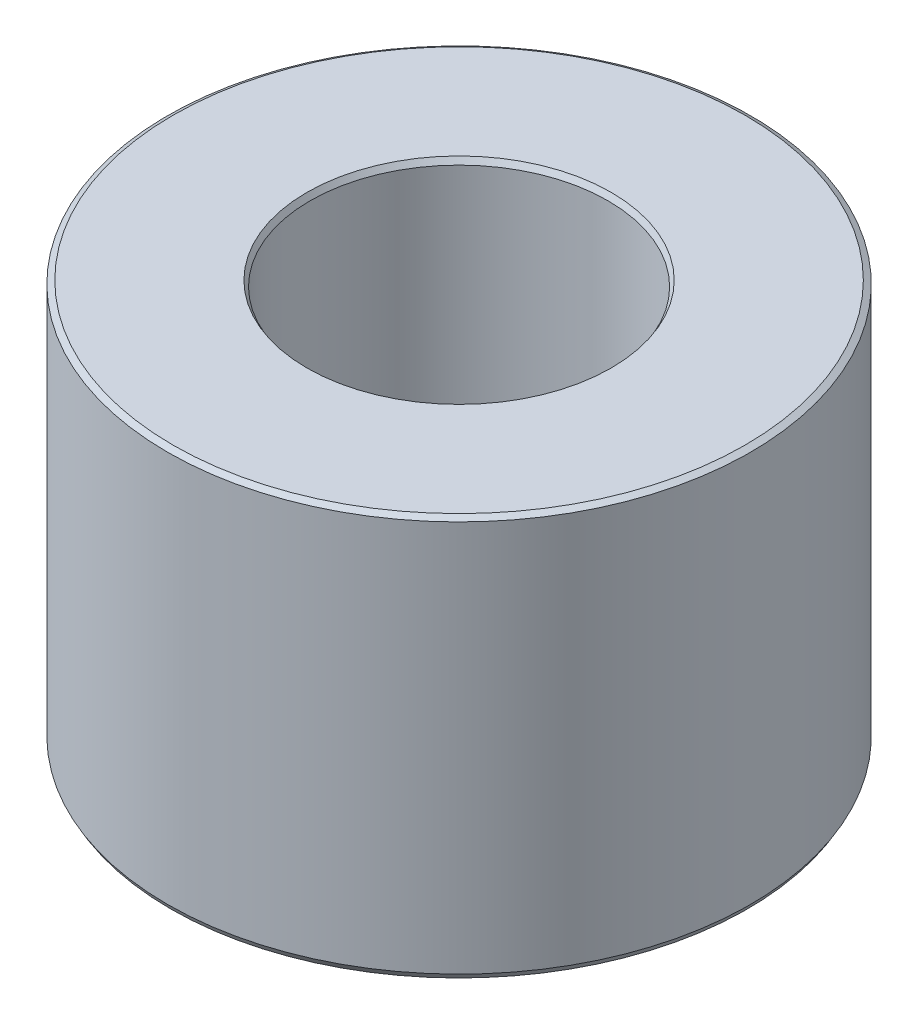
SolidWorks part; units mm, degrees
ref_plane "Front Plane" through (0, 0, 0) normal (0, 0, 1) x (1, 0, 0)
ref_plane "Top Plane" through (0, 0, 0) normal (0, 1, 0) x (1, 0, 0)
ref_plane "Right Plane" through (0, 0, 0) normal (1, 0, 0) x (0, 0, -1)
sketch "Sketch1" plane through (0, 0, 0) normal (0, 1, 0) x (1, 0, 0)
  circle A0 centre (0, 0) radius 47.5
  dimension "SLEEVE_OD" = 95
extrude "Boss-Extrude1" add sketch "Sketch1" along normal blind 65.2627
sketch "Sketch2" plane through (0, 0, 0) normal (0, 1, 0) x (1, 0, 0)
  circle A0 centre (0, 0) radius 24.2636
  dimension "BORE_D" = 48.5273
extrude "Cut-Extrude1" cut sketch "Sketch2" along normal through all
chamfer "Chamfer1" distance 0.5293 angle 60 4 edges at (0, 65.2627, 24.2636) (0, 0, 24.2636) (0, 0, 47.5) (0, 65.2627, 47.5) first distance on face at (0, 65.2627, 24.2636) first distance on face at (0, 0, 24.2636) first distance on face at (0, 65.2627, 47.5)
